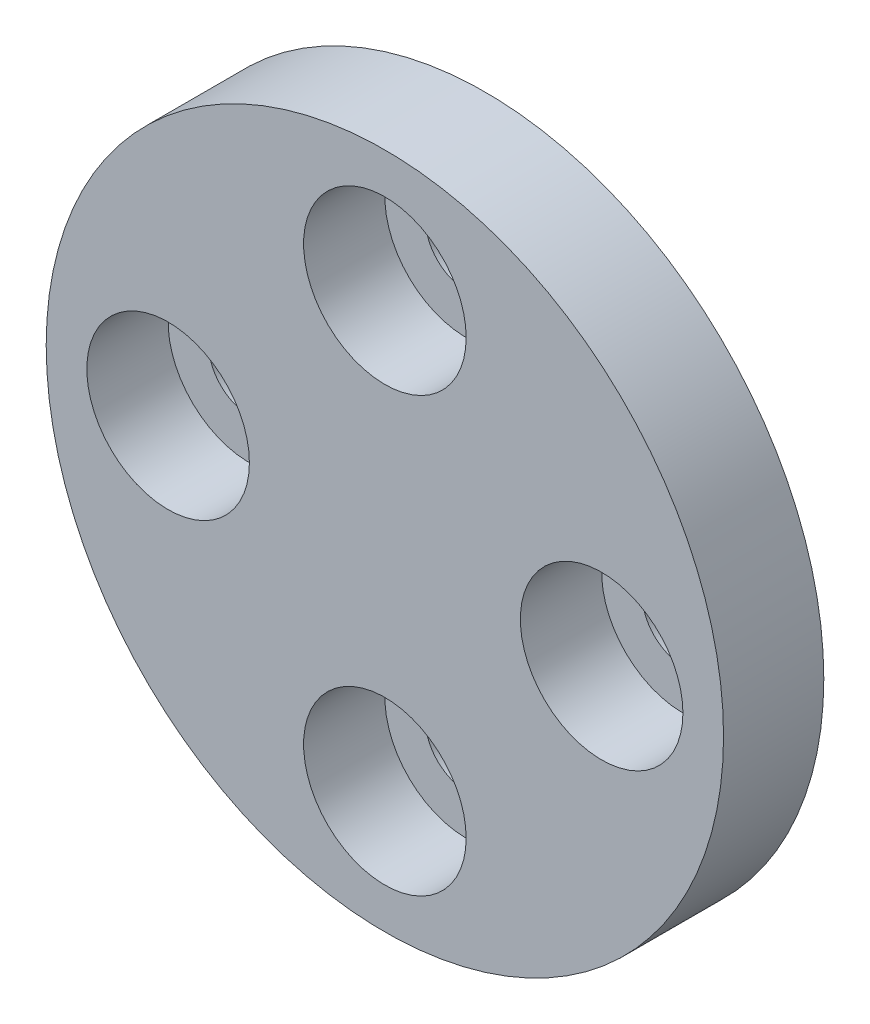
SolidWorks part; units mm, degrees
ref_plane "Ebene vorne" through (0, 0, 0) normal (0, 0, 1) x (1, 0, 0)
ref_plane "Ebene oben" through (0, 0, 0) normal (0, 1, 0) x (1, 0, 0)
ref_plane "Ebene rechts" through (0, 0, 0) normal (1, 0, 0) x (0, 0, -1)
sketch "Skizze1" plane through (0, 0, 0) normal (0, 0, 1) x (1, 0, 0)
  circle A0 centre (0, 0) radius 12.5
  circle A1 centre (0, 0) radius 9.5
  circle A2 centre (8, 0) radius 1.5
  circle A3 centre (0, -8) radius 1.5
  circle A4 centre (-8, 0) radius 1.5
  circle A5 centre (0, 8) radius 1.5
  point P15 (0, 0)
  dimension "D1" = 25
  dimension "D2" = 19
  dimension "D3" = 4
extrude "Aufsatz-Linear austragen1" add sketch "Skizze1" along normal blind 3.7 contours A0 A1 | A1 A5 A4 A3 A2 region at (-12.1464, 0, 0) region at (0, 0, 0)
sketch "Skizze2" plane through (0, 0, 3.7) normal (0, 0, 1) x (1, 0, 0)
  circle A0 centre (0, 8) radius 3
  circle A1 centre (8, 0) radius 3
  circle A2 centre (0, -8) radius 3
  circle A3 centre (-8, 0) radius 3
  point P12 (0, 0)
  dimension "D1" = 4
extrude "Schnitt-Linear austragen1" cut sketch "Skizze2" against normal blind 3
